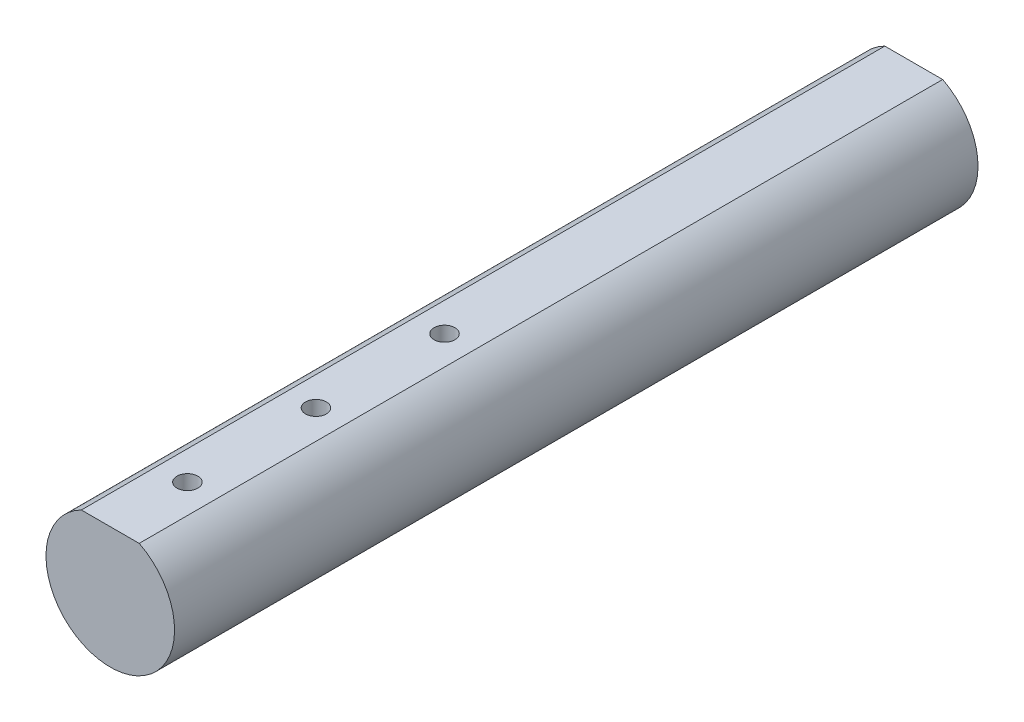
SolidWorks part; units mm, degrees
ref_plane "Front Plane" through (0, 0, 0) normal (0, 0, 1) x (1, 0, 0)
ref_plane "Top Plane" through (0, 0, 0) normal (0, 1, 0) x (1, 0, 0)
ref_plane "Right Plane" through (0, 0, 0) normal (1, 0, 0) x (0, 0, -1)
sketch "Sketch1" plane through (0, 0, 0) normal (0, 0, 1) x (1, 0, 0)
  circle A0 centre (0, 0) radius 10
  dimension "D1" = 20
extrude "Boss-Extrude1" add sketch "Sketch1" along normal mid plane 125
sketch "Sketch2" plane through (0, 0, 62.5) normal (0, 0, 1) x (1, 0, 0)
  line L0 (0, -1000) -> (0, 49000) construction
  line L1 (-4.5, 13.9303) -> (4.5, 13.9303)
  line L2 (-4.5, 13.9303) -> (-4.5, 8.9303)
  line L3 (-4.5, 8.9303) -> (4.5, 8.9303)
  line L4 (4.5, 13.9303) -> (4.5, 8.9303)
  line L5 (-4.5, 13.9303) -> (4.5, 8.9303) construction
  line L6 (-4.5, 8.9303) -> (4.5, 13.9303) construction
  circle A0 centre (0, 0) radius 10 construction
  point P0 (0, 11.4303)
  point P5 (0, 0)
  point P7 (0, 0)
  point P12 (0, 0)
  dimension "D1" = 9
  dimension "D2" = 5
extrude "Cut-Extrude1" cut sketch "Sketch2" against normal through all
sketch "Sketch3" plane through (0, 8.9303, 0) normal (0, 1, 0) x (1, 0, 0)
  line L0 (0, -1000) -> (0, 49000) construction
  line L1 (-4.5, -62.5) -> (4.5, -62.5) construction
  circle A0 centre (0, -50.5) radius 1.625
  circle A1 centre (0, -30.5) radius 1.625
  circle A2 centre (0, -10.5) radius 1.625
  dimension "D4" = 3.25
  dimension "D5" = 3.25
  dimension "D6" = 3.25
  dimension "D1" = 12
  dimension "D2" = 20
  dimension "D3" = 20
extrude "Cut-Extrude2" cut sketch "Sketch3" against normal through all
sketch "Sketch4" plane through (0, 8.9303, 0) normal (0, 1, 0) x (1, 0, 0)
  circle A0 centre (0, -10.5) radius 4
  circle A1 centre (0, -30.5) radius 4
  circle A2 centre (0, -50.5) radius 4
  dimension "D1" = 8
  dimension "D2" = 8
  dimension "D3" = 8
extrude "Cut-Extrude3" cut sketch "Sketch4" against normal blind 150 from offset 8 offset against normal yes
